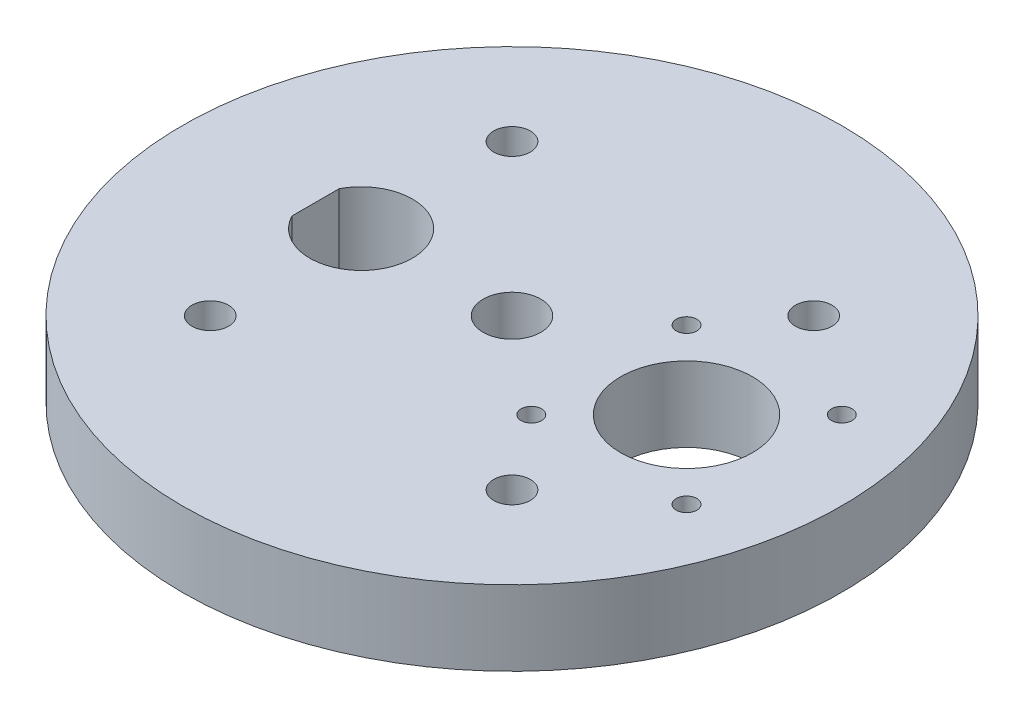
SolidWorks part; units mm, degrees
ref_plane "Front Plane" through (0, 0, 0) normal (0, 0, 1) x (1, 0, 0)
ref_plane "Top Plane" through (0, 0, 0) normal (0, 1, 0) x (1, 0, 0)
ref_plane "Right Plane" through (0, 0, 0) normal (1, 0, 0) x (0, 0, -1)
sketch "Sketch2" plane through (0, 0, 0) normal (0, 1, 0) x (1, 0, 0)
  circle A0 centre (0, 0) radius 57.15
  dimension "D1" = 114.3
extrude "Boss-Extrude1" add sketch "Sketch2" along normal blind 13 contours A0
sketch "Sketch6" plane through (0, 13, 0) normal (0, 1, 0) x (1, 0, 0)
  circle A0 centre (-26.1629, -26.1629) radius 3.175
  circle A1 centre (26.1629, -26.1629) radius 3.175
  circle A2 centre (-26.1629, 26.1631) radius 3.175
  circle A3 centre (26.1629, 26.1631) radius 3.175
  dimension "D1" = 6.35
  dimension "D2" = 74
  dimension "D3" = 26.1629
  dimension "D4" = 26.1629
  dimension "D5" = 26.1629
extrude "Cut-Extrude1" cut sketch "Sketch6" against normal up to next
sketch "Sketch7" plane through (0, 13, 0) normal (0, 1, 0) x (1, 0, 0)
  circle A0 centre (30, 0.2699) radius 11.43
  circle A3 centre (16.54, -13.1941) radius 1.778
  circle A4 centre (16.54, 13.7299) radius 1.778
  circle A5 centre (43.46, 13.7299) radius 1.778
  circle A6 centre (43.46, -13.1941) radius 1.778
  dimension "D1" = 22.86
  dimension "D2" = 3.556
  dimension "D3" = 3.556
  dimension "D4" = 3.556
  dimension "D5" = 3.556
  dimension "D6" = 13.46
  dimension "D7" = 13.46
  dimension "D8" = 13.46
  dimension "D9" = 13.464
  dimension "D10" = 30
extrude "Cut-Extrude2" cut sketch "Sketch7" against normal through all
sketch "Sketch8" plane through (0, 13, 0) normal (0, 1, 0) x (1, 0, 0)
  line L0 (-34.0629, 4.0988) -> (-34.0629, -4.0988)
  circle A2 centre (0, 0) radius 5
  arc A3 (-34.0629, -4.0988) -> (-34.0629, 4.0988) centre (-26.1629, 0) ccw
  circle A4 centre (-26.1629, 26.1631) radius 3.175 construction
  point P8 (0, 0)
  dimension "D1" = 7.9
  dimension "D2" = 0
  dimension "D3" = 10
  dimension "D4" = 17.8
extrude "Cut-Extrude3" cut sketch "Sketch8" against normal through all
equation "\"width\"=26.1629"
equation "\"D4@Sketch6\"=\"width\""
equation "\"D3@Sketch6\"=\"width\""
equation "\"D5@Sketch6\"=\"width\""
